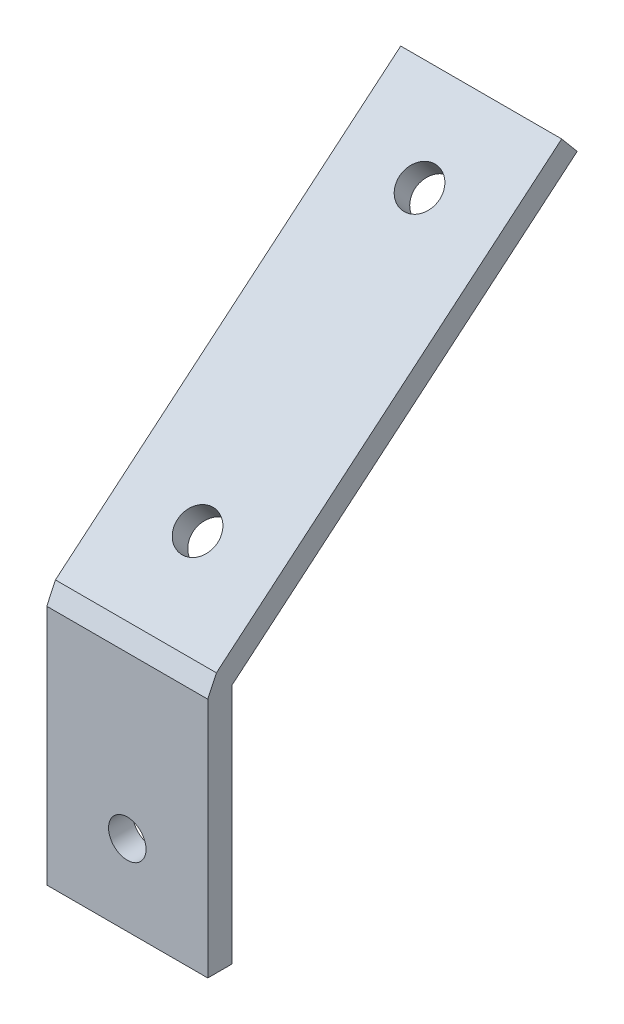
SolidWorks part; units mm, degrees
ref_plane "前视基准面" through (0, 0, 0) normal (0, 0, 1) x (1, 0, 0)
ref_plane "上视基准面" through (0, 0, 0) normal (0, 1, 0) x (1, 0, 0)
ref_plane "右视基准面" through (0, 0, 0) normal (1, 0, 0) x (0, 0, -1)
sketch "草图2" plane through (0, 0, 0) normal (1, 0, 0) x (0, 0, -1)
  line L0 (3, 30) -> (1.0716, 32.2981)
  line L1 (0, 0) -> (3, 0)
  line L2 (0, 0) -> (0, 30)
  line L3 (0, 30) -> (3, 30)
  line L4 (3, 0) -> (3, 30)
  line L5 (3, 30) -> (45.8985, 65.9961)
  line L6 (1.0716, 32.2981) -> (43.9701, 68.2942)
  line L7 (45.8985, 65.9961) -> (43.9701, 68.2942)
  line L8 (1.0716, 32.2981) -> (0, 30)
  dimension "D1" = 3
  dimension "D2" = 30
  dimension "D3" = 3
  dimension "D4" = 56
extrude "凸台-拉伸1" add sketch "草图2" along normal blind 20 contours L5 L7 L6 L0 | L0 L8 L3 | L1 L4 L3 L2 region at (0, 30.766, -1.3572) region at (0, 15, -1.5) region at (0, 49.1471, -23.4851)
ref_plane "基准面1" through (0, 16.1275, 13.5326) normal (0, -0.766, -0.6428) x (-1, 0, 0)
sketch "草图3" plane through (0, 16.1275, 13.5326) normal (0, -0.766, -0.6428) x (-1, 0, 0)
  line L0 (-20, 21.5818) -> (0, 21.5818) construction
  line L1 (0, 21.5818) -> (0, 77.5818) construction
  circle A0 centre (-10, 67.5818) radius 2.5
  circle A1 centre (-10, 31.5818) radius 2.5
  point P8 (0, 0)
  dimension "D1" = 5
  dimension "D2" = 5
  dimension "D3" = 36
  dimension "D4" = 10
  dimension "D5" = 10
extrude "切除-拉伸1" cut sketch "草图3" against normal up to next
sketch "草图4" plane through (0, 0, -3) normal (0, 0, -1) x (-1, 0, 0)
  line L0 (-20, 0) -> (0, 0) construction
  line L1 (0, 0) -> (0, 30) construction
  circle A1 centre (-10, 10) radius 2.3287
  dimension "D1" = 10
  dimension "D2" = 10
extrude "切除-拉伸2" cut sketch "草图4" against normal blind 100 contours A1 region at (10, 10, -3)
